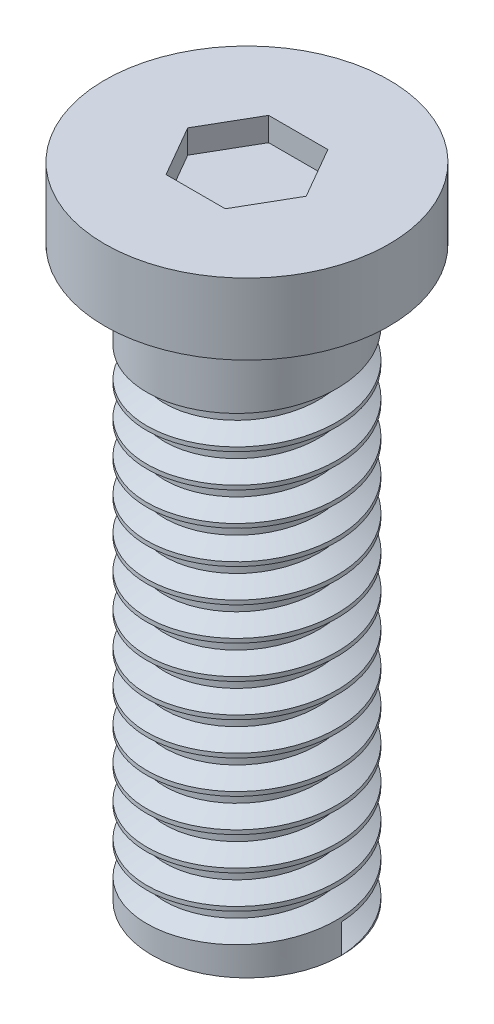
SolidWorks part; units mm, degrees
ref_plane "Front" through (0, 0, 0) normal (0, 0, 1) x (1, 0, 0)
ref_plane "Top" through (0, 0, 0) normal (0, 1, 0) x (1, 0, 0)
ref_plane "Right" through (0, 0, 0) normal (1, 0, 0) x (0, 0, -1)
sketch "Sketch1" plane through (0, 0, 0) normal (0, 1, 0) x (1, 0, 0)
  circle A0 centre (0, 0) radius 2
  dimension "D1" = 4
extrude "Boss-Extrude1" add sketch "Sketch1" along normal blind 12
sketch "Sketch2" plane through (0, 12, 0) normal (0, 1, 0) x (1, 0, 0)
  circle A1 centre (0, 0) radius 3
  dimension "D1" = 6
extrude "Boss-Extrude2" add sketch "Sketch2" along normal blind 1.5
sketch "Sketch3" plane through (0, 13.5, 0) normal (0, 1, 0) x (1, 0, 0)
  line L1 (0.625, -1.0825) -> (1.25, 0)
  line L2 (1.25, 0) -> (0.625, 1.0825)
  line L3 (0.625, 1.0825) -> (-0.625, 1.0825)
  line L4 (-0.625, 1.0825) -> (-1.25, 0)
  line L5 (-1.25, 0) -> (-0.625, -1.0825)
  line L6 (-0.625, -1.0825) -> (0.625, -1.0825)
  circle A0 centre (0, 0) radius 1.0825 construction
  point P1 (-1.0825, -0.4686)
  dimension "D1" = 1.25
extrude "Cut-Extrude1" cut sketch "Sketch3" against normal blind 0.5
thread "Thread1" pitch 0.7 method cut profile "Thread Profile1" start angle 0, offset 0, length 10, pitch 0.7, diameter 4
ref_plane "Plane1" through (2, 0, 0) normal (0, 0, 1) x (1, 0, 0)
sketch "Thread Profile1" plane through (2, 0, 0) normal (0, 0, 1) x (1, 0, 0)
  line L0 (0, 0) -> (0, 0.7) construction
  line L11 (0, 0) -> (0, 0.6125)
  line L12 (0, 0.6125) -> (-0.3789, 0.3937)
  line L13 (-0.3789, 0.3937) -> (-0.3789, 0.2187)
  line L15 (-0.3789, 0.2187) -> (0, 0)
  line L17 (-0.3789, 0.3062) -> (0, 0.3062) construction
  point P2 (0, 0)
  dimension "Pitch" = 0.7
  dimension "Profile_Angle" = 60
  dimension "Profile_Land" = 0.175
  dimension "Profile_Height" = 0.3789
